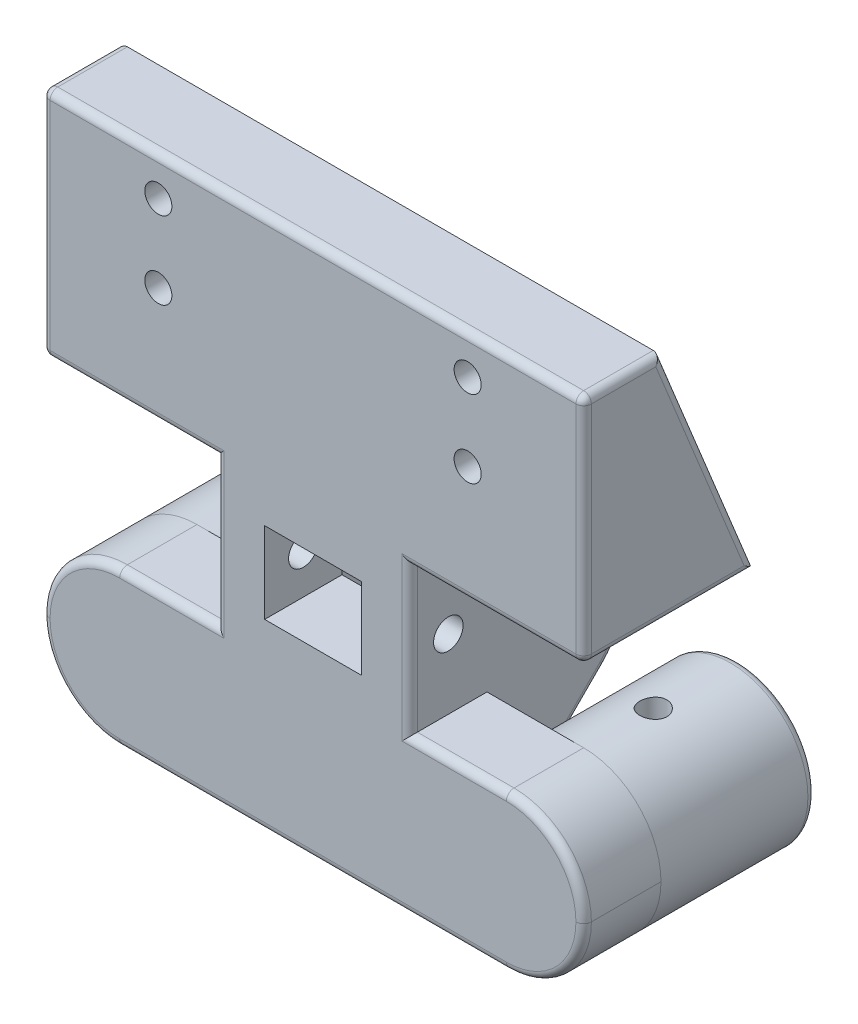
SolidWorks part; units mm, degrees
ref_plane "Front Plane" through (0, 0, 0) normal (0, 0, 1) x (1, 0, 0)
ref_plane "Top Plane" through (0, 0, 0) normal (0, 1, 0) x (1, 0, 0)
ref_plane "Right Plane" through (0, 0, 0) normal (1, 0, 0) x (0, 0, -1)
sketch "Sketch1" plane through (0, 0, 0) normal (0, 0, 1) x (1, 0, 0)
  line L1 (-35, 10) -> (35, 10)
  line L2 (-35, 10) -> (-35, -10)
  line L3 (-35, -10) -> (35, -10)
  line L4 (35, 10) -> (35, -10)
  line L5 (-35, 10) -> (35, -10) construction
  line L6 (-35, -10) -> (35, 10) construction
  point P0 (0, 0)
  dimension "D1" = 70
  dimension "D2" = 20
extrude "Boss-Extrude1" add sketch "Sketch1" along normal blind 10
sketch "Sketch2" plane through (0, 0, 0) normal (0, 0, -1) x (-1, 0, 0)
  circle A0 centre (-25, 0) radius 10
  circle A1 centre (25, 0) radius 10
  circle A2 centre (25, 0) radius 6.4
  circle A3 centre (-25, 0) radius 6.4
  dimension "D1" = 12.8
  dimension "D2" = 20
  dimension "D3" = 25
  dimension "D4" = 25
extrude "Boss-Extrude2" add sketch "Sketch2" along normal blind 20
sketch "Sketch3" plane through (0, 0, 0) normal (0, 1, 0) x (1, 0, 0)
  line L0 (-18.6, 0) -> (-31.4, 0) construction
  circle A0 centre (-25, 9) radius 1.75
  circle A1 centre (25, 9) radius 1.75
  dimension "D2" = 3.5
  dimension "D1" = 9
extrude "Cut-Extrude1" cut sketch "Sketch3" against normal through all both and the other way through all
sketch "Sketch4" plane through (0, 0, 10) normal (0, 0, 1) x (1, 0, 0)
  line L0 (35, 10) -> (-35, 10) construction
  line L1 (-12.5, 10) -> (12.5, 10)
  line L2 (-12.5, 10) -> (-12.5, 59)
  line L3 (-12.5, 59) -> (12.5, 59)
  line L4 (12.5, 10) -> (12.5, 59)
  point P6 (0, 59)
  dimension "D1" = 25
  dimension "D2" = 49
extrude "Boss-Extrude3" add sketch "Sketch4" against normal up to surface (10 mm away) up to face at (0, 0, 0)
sketch "Sketch6" plane through (0, 0, 10) normal (0, 0, 1) x (1, 0, 0)
  line L1 (-6.25, 24.25) -> (6.25, 24.25)
  line L2 (-6.25, 24.25) -> (-6.25, 13.75)
  line L3 (-6.25, 13.75) -> (6.25, 13.75)
  line L4 (6.25, 24.25) -> (6.25, 13.75)
  line L5 (-6.25, 24.25) -> (6.25, 13.75) construction
  line L6 (-6.25, 13.75) -> (6.25, 24.25) construction
  point P0 (0, 19)
  dimension "D1" = 19
  dimension "D2" = 10.5
  dimension "D3" = 12.5
extrude "Cut-Extrude2" cut sketch "Sketch6" against normal through all
sketch "Sketch7" plane through (-12.5, 0, 0) normal (-1, 0, 0) x (0, 0, 1)
  line L0 (10, 59) -> (10, 10) construction
  circle A0 centre (5, 19) radius 1.9096
  dimension "D1" = 3.8193
  dimension "D2" = 5
extrude "Cut-Extrude3" cut sketch "Sketch7" against normal through all
sketch "Sketch8" plane through (0, 0, 10) normal (0, 0, 1) x (1, 0, 0)
  line L1 (35, 29) -> (-35, 29)
  line L2 (35, 29) -> (35, 59)
  line L3 (35, 59) -> (-35, 59)
  line L4 (-35, 29) -> (-35, 59)
  line L5 (35, 29) -> (-35, 59) construction
  line L6 (35, 59) -> (-35, 29) construction
  point P0 (0, 44)
  dimension "D1" = 30
  dimension "D2" = 70
extrude "Boss-Extrude4" add sketch "Sketch8" against normal up to surface (10 mm away) up to face at (0, 19, 0)
sketch "Sketch9" plane through (12.5, 0, 0) normal (1, 0, 0) x (0, 0, -1)
  line L0 (0, -10) -> (0, 29)
  line L3 (20, -10) -> (20, 10) construction
  line L4 (20, 10) -> (12.2449, 29)
  line L5 (12.2449, 29) -> (0, 29)
  line L6 (0, 59) -> (12.2449, 29) construction
  line L7 (0, -10) -> (20, 10)
  dimension "D1" = 20
extrude "Boss-Extrude5" add sketch "Sketch9" against normal blind 5
mirror "Mirror3" about plane through (0, 0, 0) normal (1, 0, 0) of "Boss-Extrude5"
sketch "Sketch11" plane through (0, 0, 0) normal (0, 0, -1) x (-1, 0, 0)
  line L0 (35, 29) -> (35, 59) construction
  line L1 (-35, 29) -> (35, 29)
  line L2 (-35, 29) -> (-35, 34)
  line L3 (-35, 34) -> (35, 34)
  line L4 (35, 29) -> (35, 34)
  dimension "D1" = 5
extrude "Boss-Extrude10" add sketch "Sketch11" along normal up to surface (12.2449 mm away)
sketch "Sketch12" plane through (0, 0, 0) normal (0, 0, -1) x (-1, 0, 0)
  line L0 (35, 59) -> (-35, 59) construction
  circle A0 centre (-20, 54) radius 1.75
  circle A1 centre (20, 54) radius 1.75
  circle A2 centre (-20, 44) radius 1.75
  circle A3 centre (20, 44) radius 1.75
  dimension "D3" = 3.5
  dimension "D1" = 5
  dimension "D2" = 10
  dimension "D4" = 20
  dimension "D5" = 20
extrude "Cut-Extrude4" cut sketch "Sketch12" against normal up to next
sketch "Sketch16" plane through (35, 0, 0) normal (1, 0, 0) x (0, 0, -1)
  line L0 (-10, 59) -> (0, 59)
  line L1 (0, 59) -> (12.2449, 29)
  line L2 (12.2449, 29) -> (-10, 29)
  line L3 (-10, 29) -> (-10, 59)
extrude "Boss-Extrude11" add sketch "Sketch16" against normal blind 5
mirror "Mirror4" about plane through (0, 0, 0) normal (1, 0, 0) of "Boss-Extrude11"
fillet "Fillet1" radius 10 4 edges at (-35, -10, 5) (-35, 10, 5) (35, 10, 5) (35, -10, 5)
fillet "Fillet2" radius 10 2 edges at (-10, 10, -20) (10, 10, -20)
fillet "Fillet6" radius 1 3 edges at (30, 46.5, -5.102) (0, 34, -10.2041) (-30, 46.5, -5.102)
fillet "Fillet7" radius 1 12 edges at (12.5, -2.3492, -7.6508) (12.5, 22.5759, -14.867) (7.5, 22.5759, -14.867) (7.5, -2.3492, -7.6508) (-7.5, -2.3492, -7.6508) (-7.5, 22.5759, -14.867) (-12.5, 22.5759, -14.867) (-12.5, -2.3492, -7.6508) (12.5, 10.3965, -18.0334) (7.5, 10.3965, -18.0334) (-7.5, 10.3965, -18.0334) (-12.5, 10.3965, -18.0334)
fillet "Fillet9" radius 1 3 edges at (0, 29, -12.2449) (7.7929, 29, -11.9285) (-7.7929, 29, -11.9285)
fillet "Fillet15" radius 1 6 edges at (-35, 44, 10) (-35, 29, -1.1224) (-35, 59, 5) (35, 29, -1.1224) (35, 44, 10) (35, 59, 5)
fillet "Fillet16" radius 1 4 edges at (-34.7071, 29.2929, 9.7071) (34.7071, 29.2929, 9.7071) (-23.25, 29, 10) (23.25, 29, 10)
fillet "Fillet17" radius 1 3 edges at (34.7071, 58.7071, 9.7071) (-34.7071, 58.7071, 9.7071) (0, 59, 10)
fillet "Fillet19" radius 1 8 edges at (18.75, 10, 10) (32.0711, -7.0711, 10) (0, -10, 10) (-32.0711, -7.0711, 10) (32.0711, 7.0711, 10) (-32.0711, 7.0711, 10) (-18.75, 10, 10) (-12.5, 20, 10)
fillet "Fillet20" radius 1 1 edges at (12.5, 19.5, 10)
fillet "Fillet21" radius 1 2 edges at (-35, 0, -20) (15, 0, -20)
